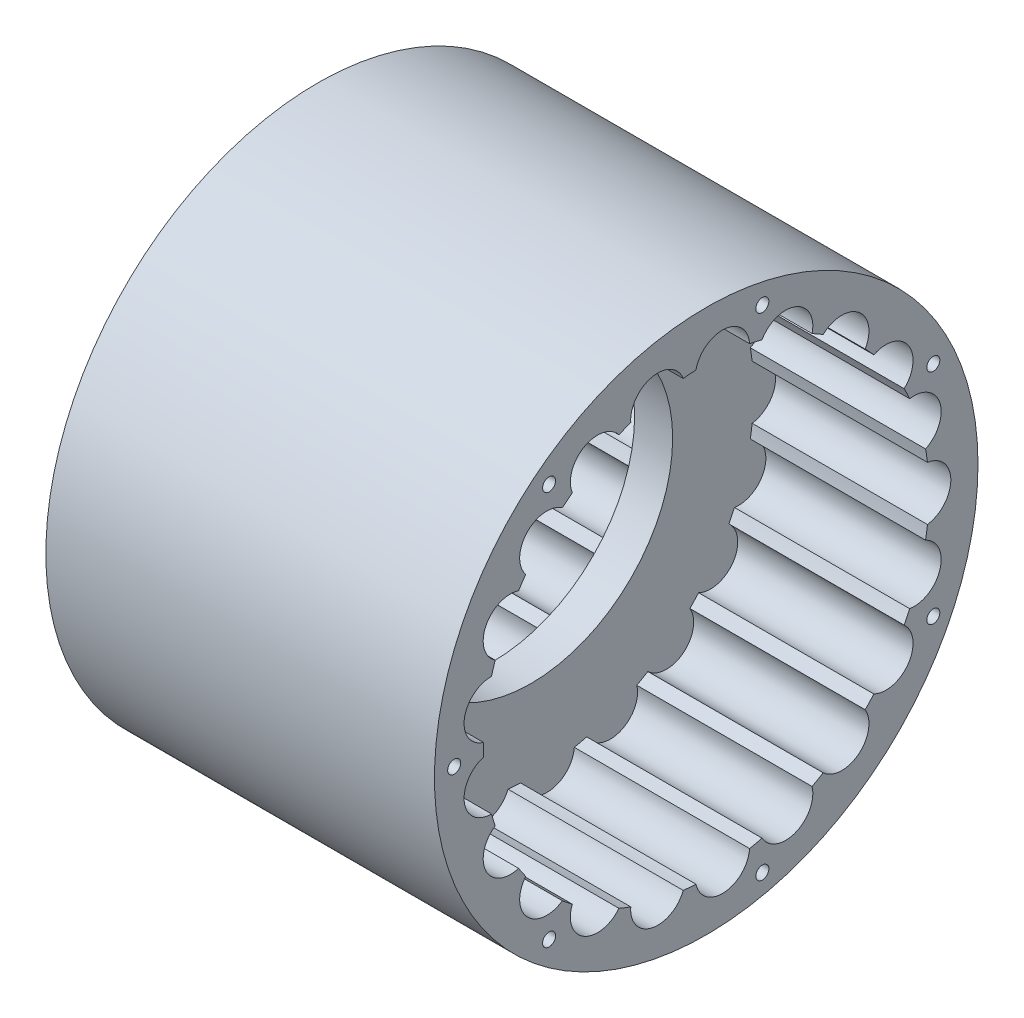
SolidWorks part; units mm, degrees
ref_plane "Ebene vorne" through (0, 0, 0) normal (0, 0, 1) x (1, 0, 0)
ref_plane "Ebene oben" through (0, 0, 0) normal (0, 1, 0) x (1, 0, 0)
ref_plane "Ebene rechts" through (0, 0, 0) normal (1, 0, 0) x (0, 0, -1)
sketch "Skizze2" plane through (0, 0, 0) normal (0, 0, 1) x (1, 0, 0)
  line L0 (0, 0) -> (-33680.1149, 0) construction
  line L1 (0, 26.075) -> (3.5, 26.075)
  line L2 (3.5, 26.075) -> (3.5, 41)
  line L3 (3.5, 41) -> (35.75, 41)
  line L4 (35.75, 41) -> (35.75, 50)
  line L5 (35.75, 50) -> (0, 50)
  line L6 (0, 50) -> (0, 26.075)
  line L7 (0, 0) -> (0, 50000) construction
  dimension "D1" = 52.15
  dimension "D2" = 3.5
  dimension "D3" = 35.75
  dimension "D4" = 100
  dimension "D5" = 82
revolve "Rotation1" add sketch "Skizze2" angle 360 about L0
sketch "Skizze4" plane through (35.75, 0, 0) normal (1, 0, 0) x (0, 0, -1)
  line L0 (0, 0) -> (-50000, 0) construction
  circle A6 centre (0, 0) radius 40 construction
  circle A7 centre (40, 0) radius 5
  circle A8 centre (38.2229, -11.7902) radius 5
  circle A9 centre (33.0496, -22.5328) radius 5
  circle A10 centre (24.9396, -31.2733) radius 5
  circle A11 centre (14.6136, -37.2349) radius 5
  circle A12 centre (2.9892, -39.8882) radius 5
  circle A13 centre (-8.9008, -38.9971) radius 5
  circle A14 centre (-20, -34.641) radius 5
  circle A15 centre (-29.3221, -27.2069) radius 5
  circle A16 centre (-36.0388, -17.3553) radius 5
  circle A17 centre (-39.5532, -5.9617) radius 5
  circle A18 centre (-39.5532, 5.9617) radius 5
  circle A19 centre (-36.0388, 17.3553) radius 5
  circle A20 centre (-29.3221, 27.2069) radius 5
  circle A21 centre (-20, 34.641) radius 5
  circle A22 centre (-8.9008, 38.9971) radius 5
  circle A23 centre (2.9892, 39.8882) radius 5
  circle A24 centre (14.6136, 37.2349) radius 5
  circle A25 centre (24.9396, 31.2733) radius 5
  circle A26 centre (33.0496, 22.5328) radius 5
  circle A27 centre (38.2229, 11.7902) radius 5
  point P8 (0, 0)
  point P49 (0, 0)
  dimension "D2" = 10
  dimension "D3" = 21
extrude "Schnitt-Linear austragen1" cut sketch "Skizze4" against normal up to surface (32.25 mm away) up to face at (3.5, 0, -41)
sketch "Skizze5" plane through (35.75, 0, 0) normal (1, 0, 0) x (0, 0, -1)
  line L0 (0, 0) -> (-50000, 0) construction
  circle A0 centre (-46.3698, 0) radius 1.2
  circle A1 centre (-28.9111, 36.2534) radius 1.2
  circle A2 centre (10.3183, 45.2073) radius 1.2
  circle A3 centre (41.7778, 20.1191) radius 1.2
  circle A4 centre (41.7778, -20.1191) radius 1.2
  circle A5 centre (10.3183, -45.2073) radius 1.2
  circle A6 centre (-28.9111, -36.2534) radius 1.2
  point P20 (0, 0)
  dimension "D1" = 2.4
extrude "Schnitt-Linear austragen2" cut sketch "Skizze5" against normal blind 13
mirror "Spiegeln1" about plane through (0, 0, 0) normal (1, 0, 0) of "Schnitt-Linear austragen2", "Schnitt-Linear austragen1", "Rotation1"
